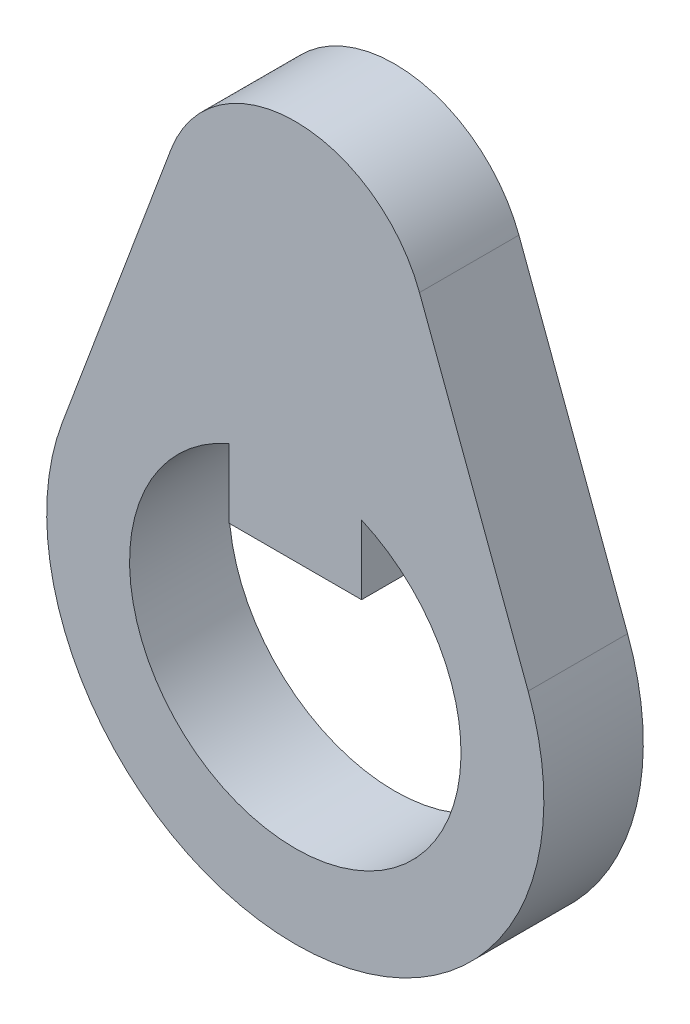
SolidWorks part; units mm, degrees
ref_plane "Front Plane" through (0, 0, 0) normal (0, 0, 1) x (1, 0, 0)
ref_plane "Top Plane" through (0, 0, 0) normal (0, 1, 0) x (1, 0, 0)
ref_plane "Right Plane" through (0, 0, 0) normal (1, 0, 0) x (0, 0, -1)
sketch "Sketch1" plane through (0, 0, 0) normal (0, 0, 1) x (1, 0, 0)
  line L0 (4, 15) -> (-4, 15)
  line L1 (4, 15) -> (4, 5)
  line L2 (4, 5) -> (-4, 5)
  line L3 (-4, 15) -> (-4, 5)
  line L4 (4, 15) -> (-4, 5) construction
  line L5 (4, 5) -> (-4, 15) construction
  line L6 (-7.494, 22.8) -> (-14.0512, 5.25)
  line L7 (7.494, 22.8) -> (14.0512, 5.25)
  circle A1 centre (0, 0) radius 10
  arc A2 (-7.494, 22.8) -> (7.494, 22.8) centre (0, 20) cw
  arc A3 (-14.0512, 5.25) -> (14.0512, 5.25) centre (0, 0) ccw
  point P3 (0, 10)
  dimension "D4" = 20
  dimension "D5" = 15
  dimension "D6" = 8
  dimension "D1" = 20
  dimension "D2" = 8
  dimension "D3" = 10
extrude "Boss-Extrude1" add sketch "Sketch1" along normal blind 6 contours L6 A3 L7 A2 A1 L3 L0 L1 | A1 L1 L0 L3 | L1 A1 L3 L2 region at (0, 12.3575, 0) region at (0, 7.3697, 0) region at (0, 27.4757, 0)
equation "\"shaftDiam\" = 20mm"
equation "\"keyW\" = 8mm"
equation "\"keyL\" = 10mm"
equation "\"clearance\" = 1mm"
equation "\"handleShaftLen\" = 60mm"
equation "\"panelH\" = 80mm"
equation "\"panelW\" = 110mm"
equation "\"D2@Sketch1\"=\"keyW\""
equation "\"D3@Sketch1\"=\"keyL\""
equation "\"D4@Sketch1\"=\"shaftDiam\""
equation "\"D5@Sketch1\"=\"shaftDiam\"*.75"
equation "\"D1@Sketch1\"=\"shaftDiam\""
equation "\"D6@Sketch1\"=\"shaftDiam\"/2.5"
equation "\"D1@Boss-Extrude1\"=\"handleShaftLen\"/10"
